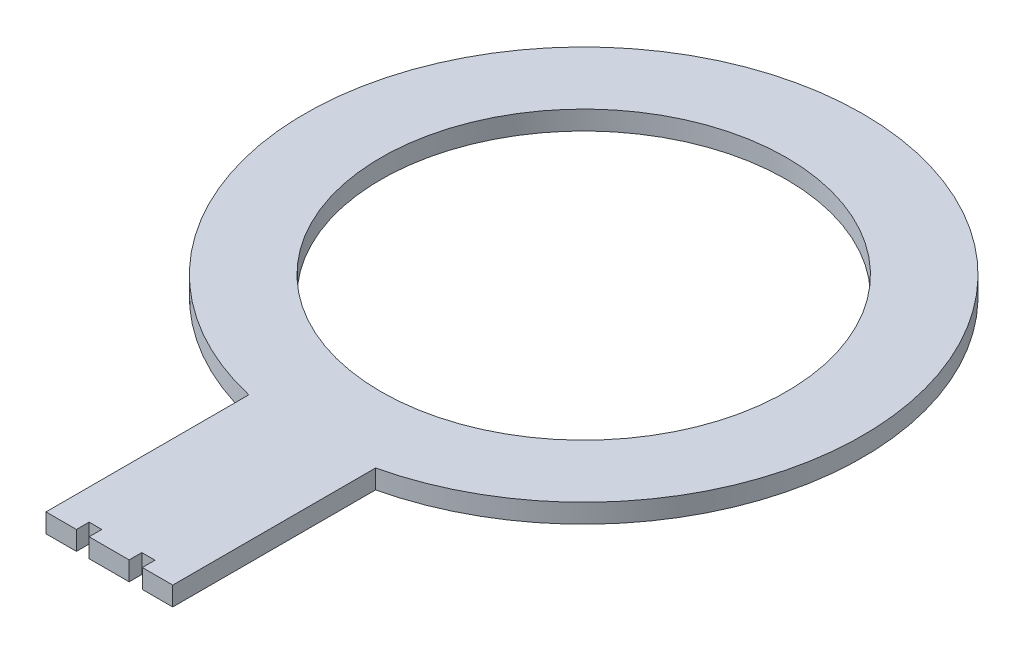
SolidWorks part; units mm, degrees
ref_plane "Front Plane" through (0, 0, 0) normal (0, 0, 1) x (1, 0, 0)
ref_plane "Top Plane" through (0, 0, 0) normal (0, 1, 0) x (1, 0, 0)
ref_plane "Right Plane" through (0, 0, 0) normal (1, 0, 0) x (0, 0, -1)
sketch "Sketch1" plane through (0, 0, 0) normal (0, 1, 0) x (1, 0, 0)
  line L0 (-8.255, -118.8221) -> (-8.255, -115.6471)
  line L1 (-8.255, -115.6471) -> (-5.08, -115.6471)
  line L2 (15.875, -68.0221) -> (15.875, -118.8221)
  line L3 (-15.875, -68.0221) -> (-15.875, -118.8221)
  line L4 (-5.08, -115.6471) -> (-5.08, -118.8221)
  line L5 (-15.875, -118.8221) -> (-8.255, -118.8221)
  line L6 (-5.08, -118.8221) -> (4.953, -118.8221)
  line L7 (4.953, -118.8221) -> (4.953, -115.6471)
  line L8 (4.953, -115.6471) -> (8.255, -115.6471)
  line L9 (8.255, -115.6471) -> (8.255, -118.8221)
  line L10 (-5.08, -118.8221) -> (4.953, -118.8221)
  line L11 (8.255, -118.8221) -> (15.875, -118.8221)
  arc A0 (15.875, -68.0221) -> (-15.875, -68.0221) centre (0, 0) ccw
  circle A1 centre (0, 0) radius 50.8
  dimension "D1" = 19.05
  dimension "D3" = 101.6
  dimension "D4" = 50.8
  dimension "D2" = 31.75
  dimension "D5" = 7.62
  dimension "D6" = 3.175
  dimension "D7" = 7.62
  dimension "D8" = 3.302
  dimension "D9" = 3.175
extrude "Boss-Extrude1" add sketch "Sketch1" along normal blind 4.7625 contours L2 A0 L3 L5 L0 L1 L4 L6 L7 L8 L9 L11 A1 region at (-12.065, 0, 116.4745)
